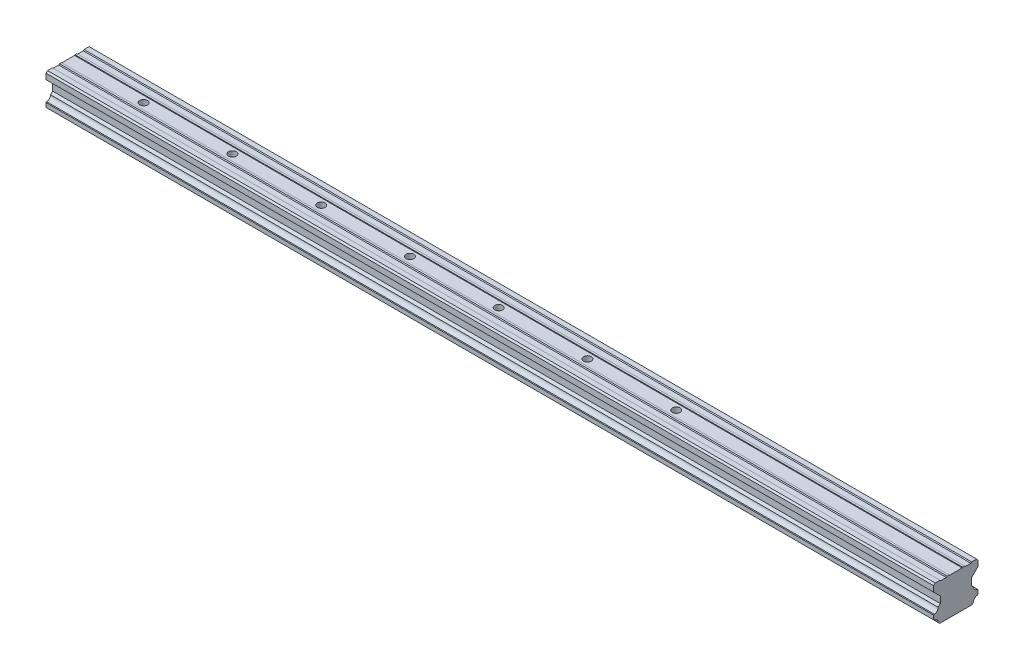
SolidWorks part; units mm, degrees
material "ASTM A36 Steel"
ref_plane "Front Plane" through (0, 0, 0) normal (0, 0, 1) x (1, 0, 0)
ref_plane "Top Plane" through (0, 0, 0) normal (0, 1, 0) x (1, 0, 0)
ref_plane "Right Plane" through (0, 0, 0) normal (1, 0, 0) x (0, 0, -1)
sketch "Sketch1" plane through (0, 0, 0) normal (1, 0, 0) x (0, 0, -1)
  line L0 (-7.9658, -7.694) -> (-7.2663, -8.3935)
  line L1 (-7.2663, -8.3935) -> (7.2663, -8.3935)
  line L2 (7.2663, -8.3935) -> (7.9658, -7.694)
  line L3 (9.7474, -5.9133) -> (10, -5.6608)
  line L4 (10, -5.6608) -> (10, -3.7884)
  line L5 (10, -3.7884) -> (9.7474, -3.5358)
  line L6 (7.9658, -1.7232) -> (7.0051, -0.7626)
  line L7 (7.0051, -0.7626) -> (7.0051, 2.1662)
  line L8 (7.0051, 2.1662) -> (10, 5.1611)
  line L9 (10, 5.1611) -> (10, 7.7124)
  line L10 (10, 7.7124) -> (9.4085, 8.3935)
  line L11 (9.4085, 8.3935) -> (7.133, 8.3935)
  line L12 (7.133, 8.3935) -> (6.7895, 8.05)
  line L13 (6.7895, 8.05) -> (4.2711, 8.05)
  line L14 (4.2711, 8.05) -> (3.9277, 8.3935)
  line L15 (3.9277, 8.3935) -> (3.0613, 8.3935)
  line L16 (3.0613, 8.3935) -> (2.872, 8.2042)
  line L17 (2.872, 8.2042) -> (-2.872, 8.2042)
  line L18 (-2.872, 8.2042) -> (-3.0613, 8.3935)
  line L19 (-3.0613, 8.3935) -> (-3.9277, 8.3935)
  line L20 (-3.9277, 8.3935) -> (-4.2712, 8.05)
  line L21 (-4.2712, 8.05) -> (-6.7895, 8.05)
  line L22 (-6.7895, 8.05) -> (-7.133, 8.3935)
  line L23 (-7.133, 8.3935) -> (-9.3077, 8.3935)
  line L24 (-9.3077, 8.3935) -> (-10, 7.7012)
  line L25 (-10, 7.7012) -> (-10, 5.1611)
  line L26 (-10, 5.1611) -> (-7.0051, 2.1662)
  line L27 (-7.0051, 2.1662) -> (-7.0051, -0.7626)
  line L28 (-7.0051, -0.7626) -> (-7.9658, -1.7232)
  line L29 (-9.7474, -5.9133) -> (-10, -5.6608)
  line L30 (-10, -5.6608) -> (-10, -3.7884)
  line L31 (-10, -3.7884) -> (-9.7474, -3.5358)
  arc A0 (-7.9658, -7.694) -> (-9.7474, -5.9133) centre (-9.7035, -7.6511) ccw
  arc A1 (-9.7474, -3.5358) -> (-7.9658, -1.7232) centre (-9.7025, -1.7981) ccw
  arc A2 (7.9658, -1.7232) -> (9.7474, -3.5358) centre (9.7025, -1.7981) ccw
  arc A3 (9.7474, -5.9133) -> (7.9658, -7.694) centre (9.7035, -7.6511) ccw
extrude "Boss-Extrude1" add sketch "Sketch1" along normal blind 400
sketch "Sketch2" plane through (0, -8.3935, 0) normal (0, -1, 0) x (1, 0, 0)
  circle A0 centre (34, 0) radius 3
  dimension "D1" = 6
  dimension "D2" = 34
hole_wizard "Hole1" positions "3DSketch1" profile "Sketch3" legacy end condition through all
sketch3d "3DSketch1"
  point P0 (34, -8.3935, 0)
sketch "Sketch3" plane through (34, -8.3935, 0) normal (1, 0, 0) x (0, 0, -1)
  line L0 (0, 0) -> (0, 16.7869)
  line L1 (0, 16.7869) -> (1.75, 16.7869)
  line L2 (1.75, 16.7869) -> (1.75, 4.5)
  line L3 (1.75, 4.5) -> (3, 4.5)
  line L4 (3, 4.5) -> (3, 0)
  line L5 (3, 0) -> (0, 0)
  line L6 (0, 110) -> (0, -10) construction
  dimension "Diameter" = 3.5
  dimension "Depth" = 16.7869
  dimension "C-Bore Diameter" = 6
  dimension "C-Bore Depth" = 4.5
sketch "Sketch4" plane through (0, -8.3935, 0) normal (0, -1, 0) x (-1, 0, 0)
  line L0 (0, 0) -> (-400, 0) construction
  line L1 (-400, -7.2663) -> (-400, 7.2663) construction
pattern_linear "LPattern1" count 7 spacing 40 along (1, 0, 0) of "Hole1"
